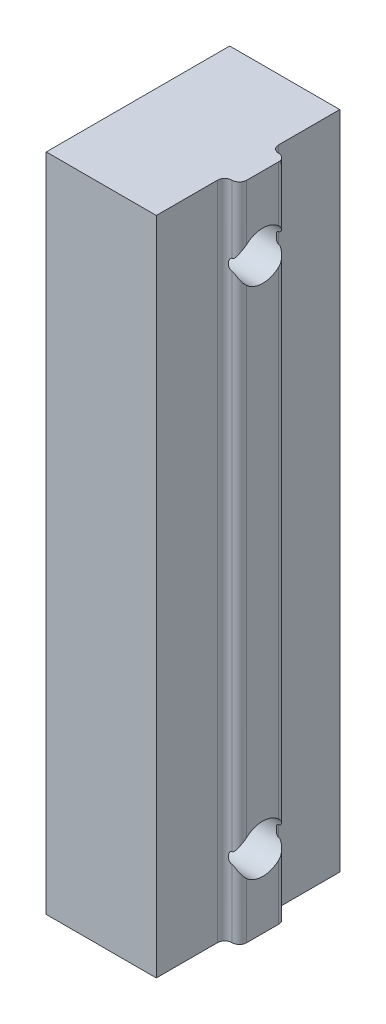
SolidWorks part; units mm, degrees
ref_plane "Front" through (0, 0, 0) normal (0, 0, 1) x (1, 0, 0)
ref_plane "Top" through (0, 0, 0) normal (0, 1, 0) x (1, 0, 0)
ref_plane "Right" through (0, 0, 0) normal (1, 0, 0) x (0, 0, -1)
sketch "Sketch2" plane through (0, 0, 0) normal (0, 0, 1) x (1, 0, 0)
  line L0 (18, 25) -> (18, 45)
  line L1 (18, 25) -> (-18, 25)
  line L2 (18, 25) -> (18, -25)
  line L3 (18, -25) -> (-18, -25)
  line L4 (-18, 25) -> (-18, -25)
  line L5 (18, 25) -> (-18, -25) construction
  line L6 (18, -25) -> (-18, 25) construction
  line L7 (33, 45) -> (-33, 45)
  line L8 (33, 45) -> (33, -45)
  line L9 (33, -45) -> (-33, -45)
  line L10 (-33, 45) -> (-33, -45)
  line L11 (33, 45) -> (-33, -45) construction
  line L12 (33, -45) -> (-33, 45) construction
  line L13 (18, -25) -> (18, -45)
  point P0 (0, 0)
  point P6 (0, 0)
  dimension "D1" = 36
  dimension "D2" = 50
  dimension "D3" = 15
  dimension "D4" = 20
extrude "Boss-Extrude1" add sketch "Sketch2" along normal blind 25 contours L2 L13 L9 L8 L7 L0 region at (25.5, 0, 0)
sketch "Sketch3" plane through (18, 0, 0) normal (1, 0, 0) x (0, 0, -1)
  line L1 (-25, 45) -> (0, 45) construction
  circle A0 centre (-12.5, 0) radius 4.8
  point P11 (-12.5, 45)
  dimension "D1" = 9.6
extrude "Cut-Extrude1" cut sketch "Sketch3" along normal blind 7.5
sketch "Sketch6" plane through (0, 45, 0) normal (0, 1, 0) x (1, 0, 0)
  line L0 (33, -25) -> (33, 0) construction
  line L1 (35, -9.325) -> (33, -9.325)
  line L2 (35, -9.325) -> (35, -15.675)
  line L3 (35, -15.675) -> (33, -15.675)
  line L4 (33, -9.325) -> (33, -15.675)
  line L5 (35, -9.325) -> (33, -15.675) construction
  line L6 (35, -15.675) -> (33, -9.325) construction
  line L7 (18, -25) -> (18, 0) construction
  point P0 (34, -12.5)
  point P10 (18, -12.5)
  dimension "D1" = 6.35
  dimension "D2" = 2
extrude "Boss-Extrude2" add sketch "Sketch6" against normal through all
fillet "Fillet2" radius 1 4 edges at (33, 0, 9.325) (35, 0, 9.325) (33, 0, 15.675) (35, 0, 15.675)
sketch "Sketch7" plane through (18, 0, 0) normal (-1, 0, 0) x (0, 0, 1)
  line L0 (25, 45) -> (0, 45) construction
  line L1 (25, -45) -> (0, -45) construction
  line L2 (0, 45) -> (0, -45) construction
  circle A0 centre (12.5, 35) radius 3.265
  circle A1 centre (12.5, -35) radius 3.265
  dimension "D1" = 10
  dimension "D2" = 6.53
  dimension "D3" = 10
  dimension "D4" = 12.5
extrude "Cut-Extrude2" cut sketch "Sketch7" against normal through all
